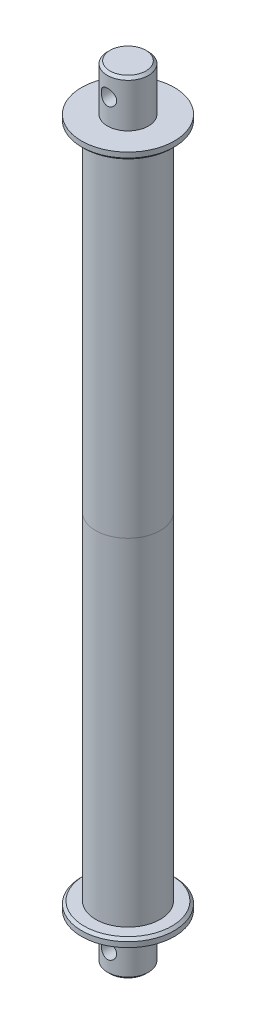
SolidWorks part; units mm, degrees
material "普通碳钢"
ref_plane "前视基准面" through (0, 0, 0) normal (0, 0, 1) x (1, 0, 0)
ref_plane "上视基准面" through (0, 0, 0) normal (0, 1, 0) x (1, 0, 0)
ref_plane "右视基准面" through (0, 0, 0) normal (1, 0, 0) x (0, 0, -1)
sketch "草图1" plane through (0, 0, 0) normal (0, 1, 0) x (1, 0, 0)
  circle A0 centre (0, 0) radius 7.95
  dimension "D1" = 15.9
extrude "凸台-拉伸1" add sketch "草图1" along normal blind 18 contours A0
chamfer "倒角2" distance 1 angle 45 1 edges at (0, 18, 7.95)
sketch "草图9" plane through (0, 0, 0) normal (0, 0, 1) x (1, 0, 0)
  line L0 (0, -8.745) -> (0, 8.745) construction
  line L1 (8.745, 0) -> (-8.745, 0) construction
  circle A0 centre (0, 9.7) radius 3
  dimension "D1" = 9.7
  dimension "D2" = 6
extrude "切除-拉伸2" cut sketch "草图9" against normal through all both and the other way through all
sketch "草图4" plane through (0, 0, 0) normal (0, 1, 0) x (1, 0, 0)
  circle A0 centre (0, 0) radius 18
extrude "凸台-拉伸2" add sketch "草图4" against normal blind 3
chamfer "倒角1" distance 1 angle 45 1 edges at (0, -3, 18)
ref_plane "基准面4" through (0, -3, 0) normal (0, -1, 0) x (-1, 0, 0)
sketch "草图5" plane through (0, -3, 0) normal (0, -1, 0) x (-1, 0, 0)
  circle A0 centre (0, 0) radius 12.5
extrude "凸台-拉伸3" add sketch "草图5" along normal blind 130.6
ref_plane "基准面5" through (0, -133.6, 0) normal (0, -1, 0) x (-1, 0, 0)
mirror "镜向3" about plane through (0, -133.6, 0) normal (0, -1, 0) of bodies 103 108
